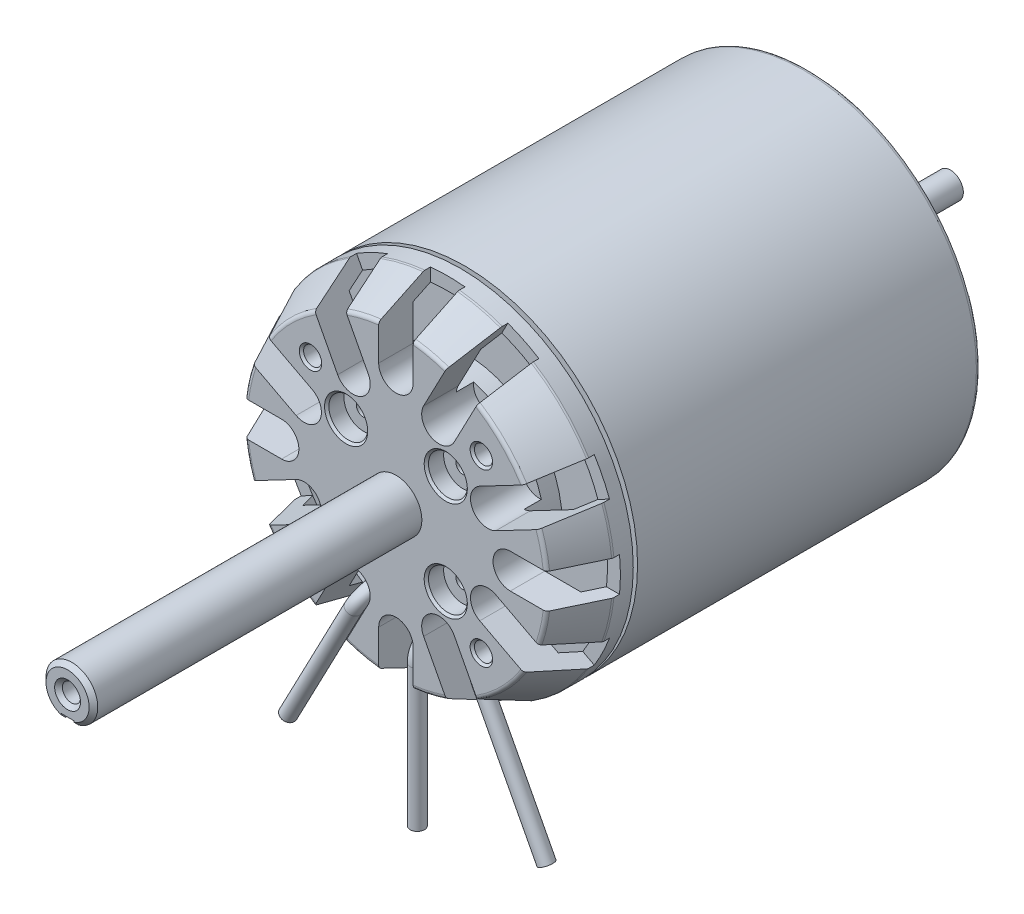
SolidWorks part; units mm, degrees
material "Titanium Ti-8Al-1Mo-1V"
ref_plane "Front Plane" through (0, 0, 0) normal (0, 0, 1) x (1, 0, 0)
ref_plane "Top Plane" through (0, 0, 0) normal (0, 1, 0) x (1, 0, 0)
ref_plane "Right Plane" through (0, 0, 0) normal (1, 0, 0) x (0, 0, -1)
sketch "Sketch1" plane through (0, 0, 0) normal (1, 0, 0) x (0, 0, -1)
  line L0 (0, 0) -> (0, 35)
  line L1 (0, 35) -> (10.5, 40)
  line L2 (10.5, 40) -> (15, 40)
  line L3 (15, 40) -> (15, 37)
  line L4 (15, 22.5) -> (16, 22.5)
  line L5 (16, 22.5) -> (16, 40)
  line L6 (16, 40) -> (95.1, 40)
  line L7 (95.1, 40) -> (107.1, 20)
  line L8 (107.1, 20) -> (107.1, 0)
  line L9 (107.1, 0) -> (0, 0)
  line L10 (-38.6361, 0) -> (0, 0) construction
  line L11 (15, 37) -> (12, 37)
  line L12 (12, 37) -> (8, 35.0952)
  line L13 (8, 35.0952) -> (8, 22.5)
  line L14 (8, 22.5) -> (15, 22.5)
  line L15 (92.269, 35) -> (91.1, 35)
  line L16 (91.1, 35) -> (91.1, 10)
  line L17 (92.269, 35) -> (101.7715, 19.1625) construction
  arc A0 (91.1, 10) -> (99.3979, 16.8379) centre (87.105, 23.3017) ccw
  arc A1 (99.3979, 16.8379) -> (92.269, 35) centre (41.7598, 4.6945) ccw
  circle A2 centre (49.0404, 20) radius 12.5
  dimension "D16" = 25
  dimension "D1" = 107.1
  dimension "D2" = 1
  dimension "D3" = 80
  dimension "D4" = 70
  dimension "D5" = 10.5
  dimension "D6" = 15
  dimension "D7" = 45
  dimension "D8" = 40
  dimension "D9" = 12
  dimension "D10" = 8
  dimension "D11" = 3
  dimension "D12" = 5
  dimension "D13" = 16
  dimension "D14" = 20
  dimension "D15" = 5
revolve "Revolve1" add sketch "Sketch1" angle 360 about L10
fillet "Fillet1" radius 1 4 edges at (20, 0, -107.1) (40, 0, -95.1) (40, 0, -10.5) (35, 0, 0)
sketch "Sketch2" plane through (0, 0, 0) normal (0, 0, 1) x (1, 0, 0)
  line L0 (0, 43.5) -> (0, 26.5) construction
  line L1 (4, 43.5) -> (4, 26.5)
  line L2 (-4, 43.5) -> (-4, 26.5)
  line L3 (-20.653, 41.6714) -> (-9.9644, 21.2776) construction
  line L4 (-17.1102, 43.5283) -> (-6.4215, 23.1344)
  line L5 (-24.1959, 39.8146) -> (-13.5073, 19.4207)
  line L6 (20.653, 41.6714) -> (9.9644, 21.2776) construction
  line L7 (24.1959, 39.8146) -> (13.5073, 19.4207)
  line L8 (17.1102, 43.5283) -> (6.4215, 23.1344)
  line L9 (0, 0) -> (0, 26.5) construction
  line L10 (-6.4215, 23.1344) -> (-3.5429, 24.6431) construction
  circle A0 centre (0, 0) radius 35 construction
  arc A1 (4, 43.5) -> (-4, 43.5) centre (0, 43.5) ccw
  arc A2 (-4, 26.5) -> (4, 26.5) centre (0, 26.5) ccw
  arc A3 (-17.1102, 43.5283) -> (-24.1959, 39.8146) centre (-20.653, 41.6714) ccw
  arc A4 (-13.5073, 19.4207) -> (-6.4215, 23.1344) centre (-9.9644, 21.2776) ccw
  arc A5 (24.1959, 39.8146) -> (17.1102, 43.5283) centre (20.653, 41.6714) ccw
  arc A6 (6.4215, 23.1344) -> (13.5073, 19.4207) centre (9.9644, 21.2776) ccw
  point P6 (0, 35)
  point P12 (-15.3087, 31.4745)
  point P20 (15.3087, 31.4745)
  point P27 (-8.1075, 17.7347)
  point P28 (0, 22.5)
  point P29 (8.1075, 17.7347)
  dimension "D1" = 4
  dimension "D2" = 22.5
  dimension "D3" = 19.5
  dimension "D4" = 3.25
extrude "Cut-Extrude1" cut sketch "Sketch2" against normal blind 12
pattern_circular "CirPattern1" count 4 over 360 about axis through (0, 0, 38.6361) along (0, 0, 1) of "Cut-Extrude1"
sketch "Sketch3" plane through (0, 0, -107.1) normal (0, 0, -1) x (-1, 0, 0)
  line L0 (0, 44.1309) -> (0, 25.2375) construction
  line L1 (5, 44.1309) -> (5, 25.2375)
  line L2 (-5, 44.1309) -> (-5, 25.2375)
  line L3 (-15.5563, -15.5563) -> (15.5563, 15.5563) construction
  line L4 (0, 0) -> (0, 15.5563) construction
  line L5 (0, 15.5563) -> (15.5563, 15.5563) construction
  line L6 (5, 28.1256) -> (10.35, 28.1256) construction
  arc A0 (5, 44.1309) -> (-5, 44.1309) centre (0, 44.1309) ccw
  arc A1 (-5, 25.2375) -> (5, 25.2375) centre (0, 25.2375) ccw
  circle A2 centre (28.1256, 28.1256) radius 17.7756
  circle A3 centre (0, 0) radius 20.2375 construction
  point P2 (0, 34.6842)
  point P14 (0, 0)
  dimension "D1" = 10
  dimension "D2" = 44
  dimension "D3" = 5.35
extrude "Cut-Extrude2" cut sketch "Sketch3" against normal blind 12
pattern_circular "CirPattern2" count 4 over 360 about axis through (0, 0, 38.6361) along (0, 0, 1) of "Cut-Extrude2"
hole_wizard "M5 Tapped Hole1" positions "Sketch5" profile "Sketch4" tap size "M5" standard "ISO"
sketch "Sketch5" plane through (0, 0, -107.1) normal (0, 0, -1) x (-1, 0, 0)
  line L1 (-9.25, -9.25) -> (9.25, -9.25)
  line L2 (-9.25, -9.25) -> (-9.25, 9.25)
  line L3 (-9.25, 9.25) -> (9.25, 9.25)
  line L4 (9.25, -9.25) -> (9.25, 9.25)
  line L5 (-9.25, -9.25) -> (9.25, 9.25) construction
  line L6 (-9.25, 9.25) -> (9.25, -9.25) construction
  line L7 (0, 0) -> (9.25, 0) construction
  point P0 (-9.25, 9.25)
  point P2 (9.25, 9.25)
  point P4 (9.25, -9.25)
  point P6 (-9.25, -9.25)
  dimension "D1" = 18.5
sketch "Sketch4" plane through (9.25, 9.25, -107.1) normal (1, 0, 0) x (0, 1, 0)
  line L0 (0, 0) -> (0, 13.6618)
  line L1 (0, 13.6618) -> (2.1, 12.4)
  line L2 (2.1, 12.4) -> (2.1, 0)
  line L5 (2.1, 0) -> (0, 0)
  line L10 (0, 13.6618) -> (-2.1, 12.4) construction
  line L11 (0, -6.35) -> (0, 107.95) construction
  dimension "Tap Drill Dia." = 4.2
  dimension "Tap Drill Depth" = 12.4
  dimension "Drill Angle" = 118
cosmetic thread "Hole Thread2"
cosmetic thread "Hole Thread3"
cosmetic thread "Hole Thread4"
cosmetic thread "Hole Thread5"
hole_wizard "M4 Tapped Hole1" positions "Sketch7" profile "Sketch6" tap size "M4" standard "ISO" end condition through all
sketch "Sketch7" plane through (0, 0, 0) normal (1, 0, 0) x (0, 0, -1)
  line L0 (106.9575, 0) -> (98.5755, 0) construction
  spline S0 degree 3 poles (96.7798, -5) (96.8993, -5) (97.0163, -4.9698) (97.2454, -4.8507) (97.3582, -4.761) (97.5753, -4.522) (97.6778, -4.3751) (97.8229, -4.1136) (97.8698, -4.0196) (97.9607, -3.8171) (98.0047, -3.7081) (98.1294, -3.3665) (98.2036, -3.1171) (98.3344, -2.5746) (98.3913, -2.2779) (98.482, -1.6646) (98.5165, -1.3461) (98.5517, -0.8498) (98.5606, -0.6807) (98.5724, -0.3445) (98.5784, -0.0084) (98.5728, 0.3277) (98.5614, 0.6638) (98.5526, 0.8328) (98.518, 1.3301) (98.4838, 1.6496) (98.3936, 2.2653) (98.337, 2.5621) (98.2066, 3.1065) (98.1323, 3.3578) (97.9649, 3.818) (97.8745, 4.0198) (97.6807, 4.3706) (97.5762, 4.5207) (97.36, 4.7593) (97.2485, 4.8486) (97.0183, 4.9692) (96.8994, 5) (96.7798, 5) knots 0 0 0 0 0.0625 0.0625 0.125 0.125 0.1875 0.1875 0.21875 0.21875 0.25 0.25 0.3125 0.3125 0.375 0.375 0.4375 0.4375 0.46875 0.46875 0.5 0.53125 0.53125 0.5625 0.5625 0.625 0.625 0.6875 0.6875 0.75 0.75 0.8125 0.8125 0.875 0.875 0.9375 0.9375 1 1 1 1 construction
  point P0 (102.7665, 0)
sketch "Sketch6" plane through (0, 0, -102.7665) normal (0, 1, 0) x (0, 0, 1)
  line L0 (0, 0) -> (0, 40)
  line L1 (0, 40) -> (1.65, 40)
  line L2 (1.65, 40) -> (1.65, 0)
  line L5 (1.65, 0) -> (0, 0)
  line L11 (0, -6.35) -> (0, 107.95) construction
  dimension "Thru Tap Drill Dia." = 3.3
  dimension "Thru Tap Drill Depth" = 40
cosmetic thread "Hole Thread6"
hole_wizard "M4 Tapped Hole2" positions "Sketch9" profile "Sketch8" tap size "M4" standard "ISO" end condition through all
sketch "Sketch9" plane through (0, 0, 0) normal (1, 0, 0) x (0, 0, -1)
  circle A0 centre (102.7665, 0) radius 1.65 construction
  point P0 (102.7665, 0)
sketch "Sketch8" plane through (0, 0, -102.7665) normal (0, 1, 0) x (0, 0, -1)
  line L0 (0, 0) -> (0, 40)
  line L1 (0, 40) -> (1.65, 40)
  line L2 (1.65, 40) -> (1.65, 0)
  line L5 (1.65, 0) -> (0, 0)
  line L11 (0, -6.35) -> (0, 107.95) construction
  dimension "Thru Tap Drill Dia." = 3.3
  dimension "Thru Tap Drill Depth" = 40
cosmetic thread "Hole Thread7"
hole_wizard "M5 Tapped Hole2" positions "Sketch11" profile "Sketch10" tap size "M5" standard "ISO" end condition up to next
sketch "Sketch11" plane through (0, 0, 0) normal (0, 0, 1) x (1, 0, 0)
  line L0 (-19.799, 19.799) -> (19.799, 19.799)
  line L1 (-19.799, 19.799) -> (-19.799, -19.799)
  line L2 (19.799, 19.799) -> (19.799, -19.799)
  line L3 (-19.799, -19.799) -> (19.799, -19.799)
  line L4 (-19.799, 19.799) -> (19.799, -19.799) construction
  line L5 (19.799, 19.799) -> (-19.799, -19.799) construction
  line L6 (0, 0) -> (4.8927, 1.0465) construction
  point P0 (-19.799, -19.799)
  point P2 (19.799, -19.799)
  point P4 (19.799, 19.799)
  point P6 (-19.799, 19.799)
  dimension "D1" = 56
sketch "Sketch10" plane through (-19.799, -19.799, 0) normal (1, 0, 0) x (0, -1, 0)
  line L0 (0, 0) -> (0, 8)
  line L1 (0, 8) -> (2.1, 8)
  line L2 (2.1, 8) -> (2.1, 0)
  line L5 (2.1, 0) -> (0, 0)
  line L11 (0, -6.35) -> (0, 107.95) construction
  dimension "Thru Tap Drill Dia." = 4.2
  dimension "Thru Tap Drill Depth" = 8
cosmetic thread "Hole Thread8"
cosmetic thread "Hole Thread9"
cosmetic thread "Hole Thread10"
cosmetic thread "Hole Thread11"
hole_wizard "M4 Tapped Hole3" positions "Sketch13" profile "Sketch14" tap size "M4" standard "ISO"
sketch "Sketch13" plane through (0, 0, 0) normal (0, 0, 1) x (1, 0, 0)
  line L0 (-11.5435, -11.5435) -> (11.5435, -11.5435)
  line L1 (-11.5435, -11.5435) -> (-11.5435, 11.5435)
  line L2 (11.5435, -11.5435) -> (11.5435, 11.5435)
  line L3 (-11.5435, 11.5435) -> (11.5435, 11.5435)
  line L4 (-11.5435, -11.5435) -> (11.5435, 11.5435) construction
  line L5 (11.5435, -11.5435) -> (-11.5435, 11.5435) construction
  line L6 (0, 0) -> (4.9406, 0) construction
  point P0 (-11.5435, 11.5435)
  point P2 (11.5435, 11.5435)
  point P4 (11.5435, -11.5435)
  point P6 (-11.5435, -11.5435)
  dimension "D1" = 32.65
sketch "Sketch14" plane through (-11.5435, 11.5435, 0) normal (1, 0, 0) x (0, -1, 0)
  line L0 (0, 0) -> (0, 22.4914)
  line L1 (0, 22.4914) -> (1.65, 21.5)
  line L2 (1.65, 21.5) -> (1.65, 0)
  line L5 (1.65, 0) -> (0, 0)
  line L10 (0, 22.4914) -> (-1.65, 21.5) construction
  line L11 (0, -6.35) -> (0, 107.95) construction
  dimension "Tap Drill Dia." = 3.3
  dimension "Tap Drill Depth" = 21.5
  dimension "Drill Angle" = 118
cosmetic thread "Hole Thread13"
cosmetic thread "Hole Thread14"
cosmetic thread "Hole Thread15"
cosmetic thread "Hole Thread16"
sketch "Sketch15" plane through (0, 0, 0) normal (0, 0, 1) x (1, 0, 0)
  circle A0 centre (-11.5435, -11.5435) radius 4.5
  circle A1 centre (11.5435, -11.5435) radius 4.5
  circle A2 centre (11.5435, 11.5435) radius 4.5
  circle A3 centre (-11.5435, 11.5435) radius 4.5
  dimension "D1" = 9
extrude "Cut-Extrude3" cut sketch "Sketch15" against normal blind 4
chamfer "Chamfer1" distance 0.5 angle 45 8 edges at (-17.699, 19.799, 0) (-17.699, -19.799, 0) (21.899, -19.799, 0) (21.899, 19.799, 0) (16.0435, -11.5435, 0) (16.0435, 11.5435, 0) (-7.0435, 11.5435, 0) (-7.0435, -11.5435, 0)
sketch "Sketch16" plane through (0, 0, 0) normal (1, 0, 0) x (0, 0, -1)
  line L0 (4.9567, -66.8164) -> (4.9567, -34.1064)
  line L1 (9.9567, -29.1064) -> (16, -29.1064)
  line L2 (16, 40) -> (16, -40) construction
  arc A0 (4.9567, -34.1064) -> (9.9567, -29.1064) centre (9.9567, -34.1064) cw
  dimension "D1" = 5
sketch "Sketch17" plane through (0, 0, -16) normal (0, 0, 1) x (1, 0, 0)
  circle A0 centre (0, -29.1064) radius 1.65
  dimension "D1" = 3.3
sweep "Sweep1" add profiles "Sketch17" path "Sketch16"
ref_plane "Plane1" through (0.5259, -0.1295, 0) normal (0.971, -0.239, 0) x (0, 0, -1)
mirror "Mirror1" about plane through (0.5259, -0.1295, 0) normal (0.971, -0.239, 0) of "Sweep1"
ref_plane "Plane2" through (-0.5259, -0.1295, 0) normal (0.971, 0.239, 0) x (0, 0, -1)
mirror "Mirror2" about plane through (-0.5259, -0.1295, 0) normal (0.971, 0.239, 0) of "Sweep1"
sketch "Sketch18" plane through (0, 0, 0) normal (0, 0, 1) x (1, 0, 0)
  circle A0 centre (0, 0) radius 6
  dimension "D1" = 12
extrude "Boss-Extrude1" add sketch "Sketch18" along normal blind 76.1
sketch "Sketch19" plane through (0, 0, 0) normal (0, 1, 0) x (1, 0, 0)
  line L0 (0, -67.5) -> (0, -55.5) construction
  line L1 (-1.5, -67.5) -> (-1.5, -55.5)
  line L2 (1.5, -67.5) -> (1.5, -55.5)
  line L3 (-6, -76.1) -> (6, -76.1) construction
  arc A0 (-1.5, -67.5) -> (1.5, -67.5) centre (0, -67.5) ccw
  arc A1 (1.5, -55.5) -> (-1.5, -55.5) centre (0, -55.5) ccw
  point P2 (0, -61.5)
  dimension "D1" = 3
  dimension "D2" = 12
  dimension "D3" = 8.6
extrude "Cut-Extrude4" cut sketch "Sketch19" against normal up to surface (1.3095 mm away) from offset 4.5 up to face at (6, 0, 76.1) offset against normal yes
hole_wizard "M5 Tapped Hole3" positions "Sketch21" profile "Sketch20" tap size "M5" standard "ISO"
sketch "Sketch21" plane through (0, 0, 76.1) normal (0, 0, 1) x (1, 0, 0)
  point P0 (0, 0)
sketch "Sketch20" plane through (0, 0, 76.1) normal (1, 0, 0) x (0, -1, 0)
  line L0 (0, 0) -> (0, 25.2618)
  line L1 (0, 25.2618) -> (2.1, 24)
  line L2 (2.1, 24) -> (2.1, 0.9)
  line L3 (2.1, 0.9) -> (3, 0)
  line L5 (3, 0) -> (0, 0)
  line L6 (-2.1, 0.9) -> (-3, 0) construction
  line L10 (0, 25.2618) -> (-2.1, 24) construction
  line L11 (0, -6.35) -> (0, 107.95) construction
  dimension "Tap Drill Dia." = 4.2
  dimension "Tap Drill Depth" = 24
  dimension "Near C'Sink Dia." = 6
  dimension "Near C'Sink Angle" = 90
  dimension "Drill Angle" = 118
cosmetic thread "Hole Thread18"
sketch "Sketch22" plane through (0, 0, -107.1) normal (0, 0, -1) x (-1, 0, 0)
  circle A1 centre (0, 0) radius 6
  circle A2 centre (0, 0) radius 6
  dimension "D1" = 0
extrude "Boss-Extrude2" add sketch "Sketch22" along normal offset from surface (35.2 mm away) 218.4 up to face at (3, 0, 76.1)
cosmetic thread "Cosmetic Thread1" [suppressed]
chamfer "Chamfer2" distance 1 angle 45 1 edges at (6, 0, 76.1)
hole_wizard "M5 Tapped Hole4" positions "Sketch24" profile "Sketch23" tap size "M5" standard "ISO"
sketch "Sketch24" plane through (0, 0, -142.3) normal (0, 0, -1) x (-1, 0, 0)
  point P0 (0, 0)
sketch "Sketch23" plane through (0, 0, -142.3) normal (1, 0, 0) x (0, 1, 0)
  line L0 (0, 0) -> (0, 25.2618)
  line L1 (0, 25.2618) -> (2.1, 24)
  line L2 (2.1, 24) -> (2.1, 0.9)
  line L3 (2.1, 0.9) -> (3, 0)
  line L5 (3, 0) -> (0, 0)
  line L6 (-2.1, 0.9) -> (-3, 0) construction
  line L10 (0, 25.2618) -> (-2.1, 24) construction
  line L11 (0, -6.35) -> (0, 107.95) construction
  dimension "Tap Drill Dia." = 4.2
  dimension "Tap Drill Depth" = 24
  dimension "Near C'Sink Dia." = 6
  dimension "Near C'Sink Angle" = 90
  dimension "Drill Angle" = 118
cosmetic thread "Hole Thread21" [suppressed]
sketch "Sketch25" plane through (0, 0, 76.1) normal (0, 0, 1) x (1, 0, 0)
  line L0 (-1.5, -7.5) -> (-1.5, -4.5)
  line L1 (-1.5, -7.5) -> (1.5, -7.5)
  line L2 (-1.5, -4.5) -> (1.5, -4.5)
  line L3 (1.5, -7.5) -> (1.5, -4.5)
  line L4 (-1.5, -7.5) -> (1.5, -4.5) construction
  line L5 (-1.5, -4.5) -> (1.5, -7.5) construction
  line L6 (0, 0) -> (0, -6) construction
  circle A0 centre (0, 0) radius 6 construction
  point P1 (0, -6)
  dimension "D1" = 3
extrude "Cut-Extrude5" cut sketch "Sketch25" against normal blind 70
fillet "Fillet2" radius 1.5 2 edges at (1.5, -5.1547, 6.1) (-1.5, -5.1547, 6.1)
move or copy body "Body-Move/Copy1" [suppressed] bodies to move or copy 120
extrude "Cut-Extrude6" cut sketch "Sketch26" along normal through all from offset 21.4
sketch "Sketch26" plane through (0, 0, -107.1) normal (0, 0, -1) x (-1, 0, 0)
  circle A0 centre (0, 0) radius 10.431
sketch "Sketch27" plane through (0, 0, -128.5) normal (0, 0, -1) x (-1, 0, 0)
  circle A0 centre (0, 0) radius 3
  dimension "D1" = 6
extrude "Cut-Extrude7" cut sketch "Sketch27" against normal blind 12 flip side to cut
equation "\"mm\"=40"
